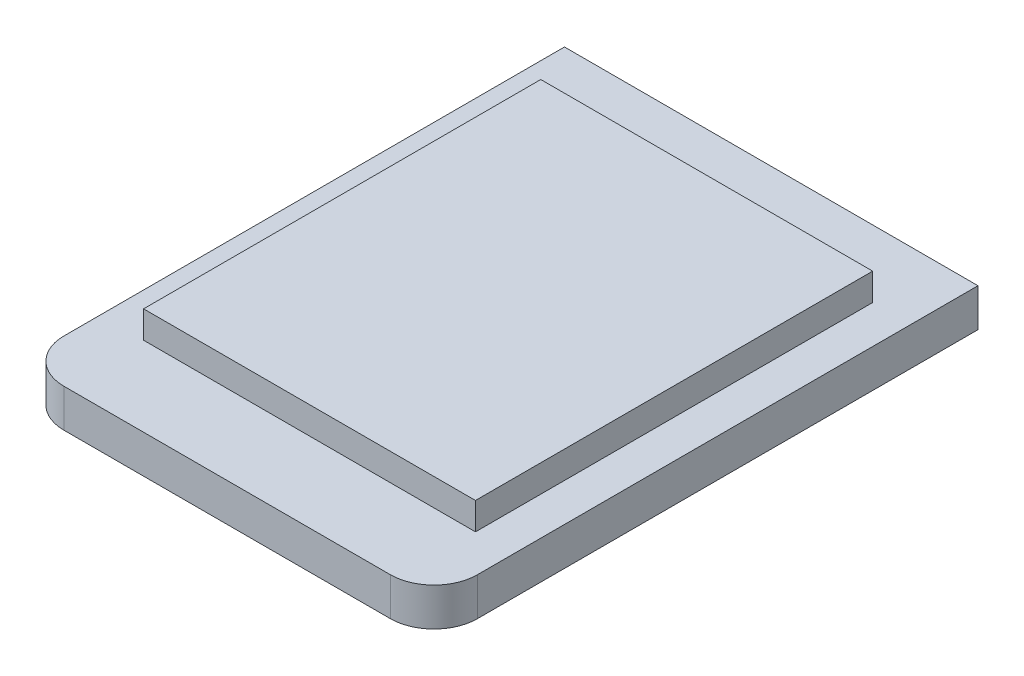
SolidWorks part; units mm, degrees
ref_plane "Front Plane" through (0, 0, 0) normal (0, 0, 1) x (1, 0, 0)
ref_plane "Top Plane" through (0, 0, 0) normal (0, 1, 0) x (1, 0, 0)
ref_plane "Right Plane" through (0, 0, 0) normal (1, 0, 0) x (0, 0, -1)
sketch "Sketch1" plane through (0, 0, 0) normal (0, 1, 0) x (1, 0, 0)
  line L1 (0, 0) -> (76, 0)
  line L2 (0, 0) -> (0, 100)
  line L3 (0, 100) -> (76, 100)
  line L4 (76, 0) -> (76, 100)
  dimension "D1" = 76
  dimension "D2" = 100
extrude "Boss-Extrude1" add sketch "Sketch1" along normal blind 7
fillet "Fillet1" radius 8 2 edges at (76, 3.5, 0) (0, 3.5, 0)
sketch "Sketch2" plane through (0, 7, 0) normal (0, 1, 0) x (1, 0, 0)
  line L1 (8, 87.6406) -> (69, 87.6406)
  line L2 (8, 87.6406) -> (8, 14.6406)
  line L3 (8, 14.6406) -> (69, 14.6406)
  line L4 (69, 87.6406) -> (69, 14.6406)
  line L5 (0, 100) -> (0, 8) construction
  point P4 (8.7814, 87.6406)
  dimension "D1" = 61
  dimension "D2" = 73
  dimension "D3" = 8
extrude "Boss-Extrude2" add sketch "Sketch2" along normal blind 5
